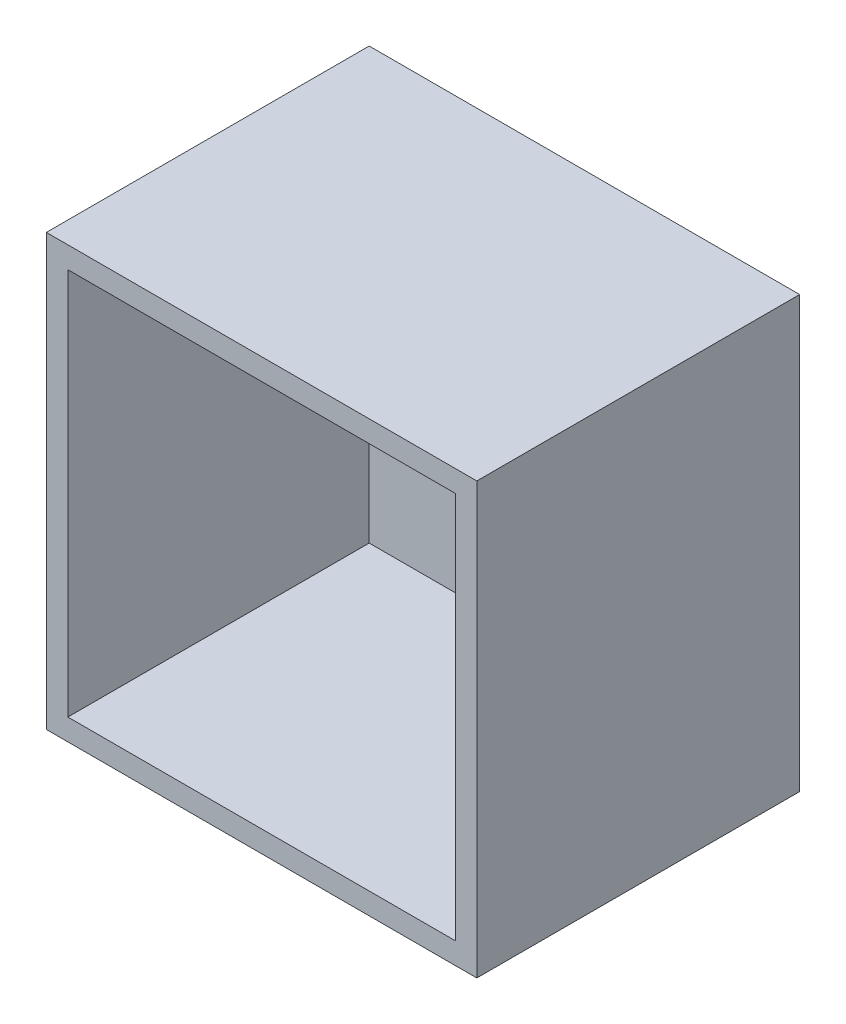
SolidWorks part; units mm, degrees
ref_plane "Front Plane" through (0, 0, 0) normal (0, 0, 1) x (1, 0, 0)
ref_plane "Top Plane" through (0, 0, 0) normal (0, 1, 0) x (1, 0, 0)
ref_plane "Right Plane" through (0, 0, 0) normal (1, 0, 0) x (0, 0, -1)
sketch "Sketch1" plane through (0, 0, 0) normal (0, 0, 1) x (1, 0, 0)
  line L0 (900, -900) -> (900, 900)
  line L1 (1000, -1000) -> (-1000, -1000)
  line L2 (1000, -1000) -> (1000, 1000)
  line L3 (1000, 1000) -> (-1000, 1000)
  line L4 (-1000, -1000) -> (-1000, 1000)
  line L5 (1000, -1000) -> (-1000, 1000) construction
  line L6 (1000, 1000) -> (-1000, -1000) construction
  line L7 (900, 900) -> (-900, 900)
  line L8 (-900, -900) -> (-900, 900)
  line L9 (900, -900) -> (-900, -900)
  point P0 (0, 0)
  dimension "D1" = 2000
  dimension "D2" = 2000
  dimension "D3" = 100
extrude "Boss-Extrude1" add sketch "Sketch1" along normal blind 100 contours L9 L0 L7 L8 region at (0, 0, 0)
extrude "Boss-Extrude2" add sketch "Sketch1<4>" along normal blind 1500 contours L4 L1 L2 L3 L0 L9 L8 L7 region at (0, -971.7157, 0)
sketch "Sketch1<4>" plane through (0, 0, 0) normal (0, 0, 1) x (1, 0, 0) same geometry as "Sketch1"
